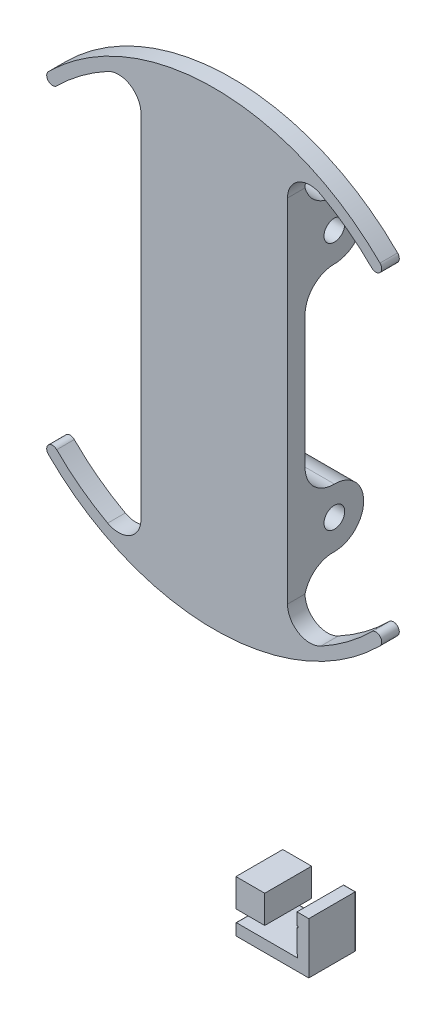
SolidWorks part; units mm, degrees
ref_plane "Front Plane" through (0, 0, 0) normal (0, 0, 1) x (1, 0, 0)
ref_plane "Top Plane" through (0, 0, 0) normal (0, 1, 0) x (1, 0, 0)
ref_plane "Right Plane" through (0, 0, 0) normal (1, 0, 0) x (0, 0, -1)
sketch "Sketch3" plane through (0, 0, 0) normal (0, 0, 1) x (1, 0, 0)
  line L0 (-35.921, -35.921) -> (-34.125, -34.125) construction
  line L1 (-15.875, -38.1) -> (0, -38.1) construction
  line L2 (-15.875, -38.1) -> (-15.875, 38.1)
  line L3 (-15.875, 38.1) -> (0, 38.1) construction
  line L4 (15.875, -38.1) -> (15.875, 38.1)
  line L5 (-15.875, -38.1) -> (15.875, 38.1) construction
  line L6 (-15.875, 38.1) -> (15.875, -38.1) construction
  line L7 (35.921, -35.921) -> (34.125, -34.125) construction
  line L8 (0, -50.8) -> (0, 50.8) construction
  line L9 (0, 38.1) -> (15.875, 38.1) construction
  line L10 (0, -38.1) -> (15.875, -38.1) construction
  line L11 (-34.125, -34.125) -> (-15.875, -15.875) construction
  line L12 (34.125, 34.125) -> (35.921, 35.921) construction
  line L13 (-15.875, -15.875) -> (0, 0) construction
  line L14 (15.875, -15.875) -> (0, 0) construction
  line L15 (-34.125, 34.125) -> (-35.921, 35.921) construction
  line L16 (34.125, -34.125) -> (15.875, -15.875) construction
  line L17 (0, 0) -> (-15.875, 15.875) construction
  line L18 (0, 0) -> (15.875, 15.875) construction
  line L19 (-15.875, 15.875) -> (-34.125, 34.125) construction
  line L20 (15.875, 15.875) -> (34.125, 34.125) construction
  arc A0 (-35.921, -35.921) -> (35.921, -35.921) centre (0, 0) ccw
  arc A1 (-34.125, -34.125) -> (-23.0827, -42.3818) centre (0, 0) ccw
  arc A2 (-15.875, 38.1) -> (-23.0827, 42.3818) centre (-20.7507, 38.1) ccw
  arc A3 (15.875, 38.1) -> (23.0827, 42.3818) centre (20.7507, 38.1) cw
  arc A4 (-15.875, -38.1) -> (-23.0827, -42.3818) centre (-20.7507, -38.1) cw
  arc A5 (15.875, -38.1) -> (23.0827, -42.3818) centre (20.7507, -38.1) ccw
  arc A6 (-35.921, 35.921) -> (-35.921, -35.921) centre (0, 0) ccw construction
  circle A7 centre (0, 0) radius 50.8 construction
  arc A8 (-34.125, 34.125) -> (-34.125, -34.125) centre (0, 0) ccw construction
  circle A9 centre (0, 0) radius 48.26 construction
  arc A10 (34.125, -34.125) -> (34.125, 34.125) centre (0, 0) ccw construction
  arc A11 (34.125, 34.125) -> (23.0827, 42.3818) centre (0, 0) ccw
  arc A12 (35.921, -35.921) -> (35.921, 35.921) centre (0, 0) ccw construction
  arc A13 (35.921, 35.921) -> (-35.921, 35.921) centre (0, 0) ccw
  arc A14 (0, 48.26) -> (-23.0827, 42.3818) centre (0, 0) ccw construction
  arc A15 (-23.0827, 42.3818) -> (-34.125, 34.125) centre (0, 0) ccw
  arc A16 (23.0827, 42.3818) -> (0, 48.26) centre (0, 0) ccw construction
  arc A17 (-23.0827, -42.3818) -> (0, -48.26) centre (0, 0) ccw construction
  arc A18 (23.0827, -42.3818) -> (34.125, -34.125) centre (0, 0) ccw
  arc A19 (0, -48.26) -> (23.0827, -42.3818) centre (0, 0) ccw construction
  arc A20 (-35.921, 35.921) -> (-34.125, 34.125) centre (-35.023, 35.023) ccw
  arc A21 (34.125, 34.125) -> (35.921, 35.921) centre (35.023, 35.023) ccw
  arc A22 (-35.921, -35.921) -> (-34.125, -34.125) centre (-35.023, -35.023) cw
  arc A23 (34.125, -34.125) -> (35.921, -35.921) centre (35.023, -35.023) cw
  point P0 (0, 0)
  point P13 (0, 0)
  point P16 (0, 0)
  point P18 (0, 0)
  dimension "D3" = 2.54
  dimension "D6" = 101.6
  dimension "D1" = 76.2
  dimension "D2" = 31.75
  dimension "D4" = 45
  dimension "D5" = 45
extrude "Main body" add sketch "Sketch3" along normal blind 3.81
ref_plane "Plane1" through (0, 0, -16.764) normal (0, 0, -1) x (-1, 0, 0)
sketch "Sketch5" plane through (15.875, 0, 0) normal (1, 0, 0) x (0, 0, -1)
  line L0 (0, 26.9938) -> (0, -26.9938)
  line L1 (0, -38.1) -> (0, 38.1) construction
  line L2 (0, 26.9938) -> (6.35, 26.9939) construction
  line L3 (6.35, 26.9939) -> (6.35, -26.9938) construction
  line L4 (6.35, -26.9938) -> (0, -26.9938) construction
  line L5 (0, 38.1) -> (0, 14.2939)
  line L6 (0, -14.2939) -> (0, -38.1)
  circle A0 centre (-0.0451, 26.9938) radius 0.0451
  arc A2 (6.35, 20.6439) -> (6.3413, 33.3438) centre (6.35, 26.9939) ccw
  arc A3 (6.0778, -33.338) -> (6.2617, -20.6445) centre (6.35, -26.9938) ccw
  arc A4 (6.35, 20.6439) -> (0, 14.2939) centre (6.3675, 14.2763) ccw
  arc A5 (6.3413, 33.3438) -> (0, 38.1) centre (6.1542, 39.6999) cw
  arc A6 (6.35, -20.6438) -> (0, -14.2939) centre (6.2623, -14.3815) cw
  arc A7 (6.35, -33.3439) -> (0, -38.1) centre (6.0797, -39.6) ccw
  arc A8 (6.3413, 33.3438) -> (0, 26.9938) centre (6.35, 26.9939) ccw construction
  arc A9 (0, 26.9938) -> (6.35, 20.6439) centre (6.35, 26.9939) ccw construction
  arc A10 (6.2617, -20.6445) -> (0, -26.9938) centre (6.35, -26.9938) ccw construction
  arc A11 (0, -26.9938) -> (6.0778, -33.338) centre (6.35, -26.9938) ccw construction
  point P5 (0, 0)
  line M6 (0, -38.1) -> (0, 38.1)
  dimension "D1" = 53.9877
  dimension "D2" = 6.35
  dimension "D3" = 12.7
  dimension "D4" = 12.7
extrude "Bosses/spacers" add sketch "Sketch5" against normal up to surface (31.75 mm away) contours A2 A5 L0 A4 M6 | A7 A3 A6 L6 M6 region at (15.875, 26.931, -5.3159) region at (15.875, -26.9385, -5.3244) up to face at (-15.875, 0, 1.905)
hole_wizard "#8 Clearance Hole1" positions "Sketch8" profile "Sketch7" hole size "#8" standard "ANSI Inch" end condition through all
sketch "Sketch8" plane through (15.875, 0, 0) normal (1, 0, 0) x (0, 0, -1)
  point P7 (6.35, 26.9939)
  point P10 (6.35, -26.8934)
sketch "Sketch7" plane through (15.875, 26.9939, -6.35) normal (0, 1, 0) x (0, 0, -1)
  line L0 (0, 0) -> (0, 52.168)
  line L1 (0, 52.168) -> (2.2479, 52.168)
  line L2 (2.2479, 52.168) -> (2.2479, 0)
  line L5 (2.2479, 0) -> (0, 0)
  line L11 (0, -6.35) -> (0, 107.95) construction
  dimension "Thru Hole Dia." = 4.4958
  dimension "Thru Hole Depth" = 52.168
sketch "Sketch26" plane through (0, 0, 0) normal (0, 0, -1) x (-1, 0, 0)
  line L6 (9.525, 0) -> (-9.525, 0) construction
  line L7 (15.875, -14.4692) -> (-15.875, -14.4692) construction
  line L8 (-15.875, -14.4692) -> (-15.875, 14.2939) construction
  line L9 (15.875, 14.2939) -> (15.875, -14.4692) construction
  line L15 (15.875, 14.2939) -> (15.875, -14.4692) construction
  line L16 (15.875, -14.4692) -> (-15.875, -14.4692) construction
  circle A0 centre (0, 9.525) radius 3.175
  arc A1 (9.525, 0) -> (-9.525, 0) centre (0, 0) ccw construction
  arc A2 (10.4775, 0) -> (-10.4775, 0) centre (0, 0) ccw
  arc A3 (8.5725, 0) -> (-8.5725, 0) centre (0, 0) ccw
  arc A4 (10.4775, 0) -> (8.5725, 0) centre (9.525, 0) cw
  arc A5 (-10.4775, 0) -> (-8.5725, 0) centre (-9.525, 0) ccw
  circle A6 centre (-9.525, 0) radius 0.9525 construction
  arc A7 (-8.5188, 0.9578) -> (-8.5607, 0.4492) centre (-8.5436, 0.7038) ccw
  arc A8 (-10.4266, 1.0318) -> (-10.4644, 0.5233) centre (-10.4486, 0.7778) cw
  circle A9 centre (9.525, 0) radius 0.9525 construction
  arc A10 (10.4268, 1.0292) -> (10.4645, 0.5226) centre (10.4487, 0.7761) ccw
  arc A11 (8.5192, 0.9548) -> (8.5608, 0.4485) centre (8.5437, 0.7019) cw
  dimension "D1" = 6.35
  dimension "D5" = 0.254
  dimension "D2" = 0.9525
  dimension "D4" = 6.35
  dimension "D6" = 0.254
  dimension "D7" = 0.254
  dimension "D8" = 0.254
  dimension "D3" = 0.9525
sketch "Sketch28" plane through (0, 0.2884, -16.764) normal (0, 0, 1) x (1, 0, 0)
  line L0 (-15.875, -20.9322) -> (-15.875, -33.6322) construction
  line L1 (-15.875, -20.9322) -> (-15.875, -33.6322) construction
  line L2 (-9.625, -115.6734) -> (-9.625, -121.7334)
  line L3 (-15.875, -126.8134) -> (-0.085, -126.8134)
  line L4 (-15.875, -126.8134) -> (-15.875, -115.6734)
  line L5 (-15.875, -115.6734) -> (-0.085, -115.6734)
  line L6 (-0.085, -126.8134) -> (-0.085, -115.6734)
  line L7 (-9.625, -121.7334) -> (-15.875, -121.7334)
  line L8 (-15.875, -124.2734) -> (-2.575, -124.2734)
  line L9 (-2.575, -124.2734) -> (-2.625, -118.6734)
  line L10 (-2.625, -118.2734) -> (-2.625, -115.6734)
  line L16 (-2.625, -118.6734) -> (-2.575, -118.6734)
  line L17 (-2.625, -123.7734) -> (-2.625, -118.6734)
  line L18 (-9.625, -124.2734) -> (-3.125, -124.2734)
  line L19 (-9.625, -115.0734) -> (-9.625, -124.2734)
  line L20 (-8.925, -115.0734) -> (-9.625, -115.0734)
  line L21 (-8.925, -115.6734) -> (-8.925, -115.0734)
  line L22 (-7.225, -115.6734) -> (-8.925, -115.6734)
  line L23 (-7.225, -117.5734) -> (-7.225, -115.6734)
  line L24 (-6.025, -117.5734) -> (-7.225, -117.5734)
  line L25 (-6.025, -115.6734) -> (-6.025, -117.5734)
  line L26 (-3.625, -115.6734) -> (-6.025, -115.6734)
  line L27 (-3.625, -115.0734) -> (-3.625, -115.6734)
  line L28 (-2.725, -115.0734) -> (-3.625, -115.0734)
  line L29 (-2.625, -118.2734) -> (-2.625, -115.1734)
  line L30 (-2.375, -118.2734) -> (-2.625, -118.2734)
  line L31 (-2.375, -118.4734) -> (-2.375, -118.2734)
  line L32 (-2.625, -118.6734) -> (-2.575, -118.6734)
  line L33 (-2.625, -123.7734) -> (-2.625, -118.6734) construction
  line L34 (-9.625, -124.2734) -> (-3.125, -124.2734) construction
  line L35 (-9.625, -115.0734) -> (-9.625, -124.2734) construction
  line L36 (-8.925, -115.0734) -> (-9.625, -115.0734) construction
  line L37 (-8.925, -115.6734) -> (-8.925, -115.0734) construction
  line L38 (-7.225, -115.6734) -> (-8.925, -115.6734) construction
  line L39 (-7.225, -117.5734) -> (-7.225, -115.6734) construction
  line L40 (-6.025, -117.5734) -> (-7.225, -117.5734) construction
  line L41 (-6.025, -115.6734) -> (-6.025, -117.5734) construction
  line L42 (-3.625, -115.6734) -> (-6.025, -115.6734) construction
  line L43 (-3.625, -115.0734) -> (-3.625, -115.6734) construction
  line L44 (-2.725, -115.0734) -> (-3.625, -115.0734) construction
  line L45 (-2.625, -118.2734) -> (-2.625, -115.1734) construction
  line L46 (-2.375, -118.2734) -> (-2.625, -118.2734)
  line L47 (-2.375, -118.4734) -> (-2.375, -118.2734)
  arc A3 (-3.125, -124.2734) -> (-2.625, -123.7734) centre (-3.125, -123.7734) ccw
  arc A4 (-3.125, -124.2734) -> (-2.625, -123.7734) centre (-3.125, -123.7734) ccw construction
  arc A5 (-2.625, -115.1734) -> (-2.725, -115.0734) centre (-2.725, -115.1734) ccw
  arc A6 (-2.625, -115.1734) -> (-2.725, -115.0734) centre (-2.725, -115.1734) ccw construction
  arc A7 (-2.575, -118.6734) -> (-2.375, -118.4734) centre (-2.575, -118.4734) ccw
  arc A8 (-2.575, -118.6734) -> (-2.375, -118.4734) centre (-2.575, -118.4734) ccw
  dimension "D2" = 2.54
  dimension "D3" = 2.54
  dimension "D4" = 2.54
  dimension "D1" = 0
extrude "Hot wire cutter base" add sketch "Sketch28" along normal up to surface (7.1752 mm away) rebuild error yes up to face at (0, -26.9939, -9.525)
extrude "Hot wire cutter fingers" add sketch "Sketch28<3>" against normal blind 10.16 contours L2 L7 L4 L5 | L32 A8 L47 L46 L10 L5 L6 L3 L4 L8 L9 region at (-12.75, -118.415, -16.764) region at (-6.375, -124.1782, -16.764)
sketch "Sketch28<3>" plane through (0, 0.2884, -16.764) normal (0, 0, 1) x (1, 0, 0) same geometry as "Sketch28"
fillet "Hot wire cutter fillet" radius 0.127 11 edges at (-2.6, -121.185, -26.924) (-9.225, -123.985, -26.924) (-15.875, -125.255, -26.924) (-7.98, -126.525, -26.924) (-0.085, -120.955, -26.924) (-1.355, -115.385, -26.924) (-2.625, -116.685, -26.924) (-2.5, -117.985, -26.924) (-2.375, -118.085, -26.924) (-2.4336, -118.3264, -26.924) (-15.875, -123.985, -21.844)
extrude "Monofilament slot" cut sketch "Sketch26" against normal through all contours A2 A0 | A3 A0 A2 | A0 A3 | A3 A11 A4 A2 A10 A0 | A2 A8 A5 A3 A7 A0 rebuild error yes
fillet "Fillet4" radius 2.54 rebuild error yes
fillet "Fillet5" radius 0.508 rebuild error yes
sketch "Sketch27" plane through (0, 0, 0) normal (0, 0, -1) x (-1, 0, 0)
  line L0 (7.62, 0) -> (-7.62, 0) construction
  text T0 "> <" font "Century Gothic" height 6.35
  point P4 (0, 0)
  dimension "D1" = 15.24
extrude "Cut-Extrude1 eyes" cut sketch "Sketch27" against normal blind 0.508 rebuild error yes
